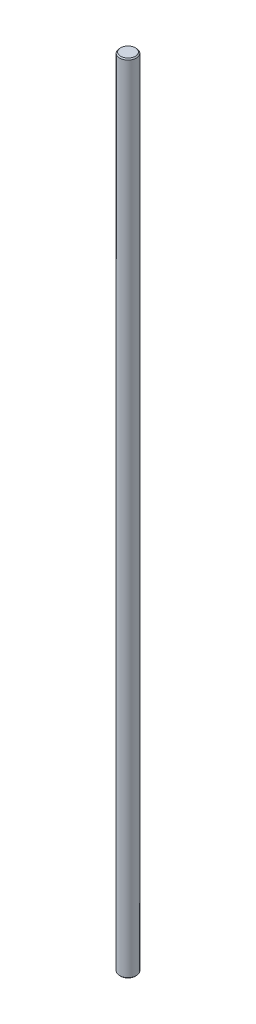
SolidWorks part; units mm, degrees
ref_plane "Front Plane" through (0, 0, 0) normal (0, 0, 1) x (1, 0, 0)
ref_plane "Top Plane" through (0, 0, 0) normal (0, 1, 0) x (1, 0, 0)
ref_plane "Right Plane" through (0, 0, 0) normal (1, 0, 0) x (0, 0, -1)
sketch "Sketch1" plane through (0, 0, 0) normal (0, 1, 0) x (1, 0, 0)
  circle A0 centre (0, 0) radius 4
  dimension "D1" = 8
extrude "Boss-Extrude1" add sketch "Sketch1" along normal blind 190 and the other way blind 190
chamfer "Chamfer1" distance 0.5 angle 45 2 edges at (0, -190, 4) (0, 190, 4)
